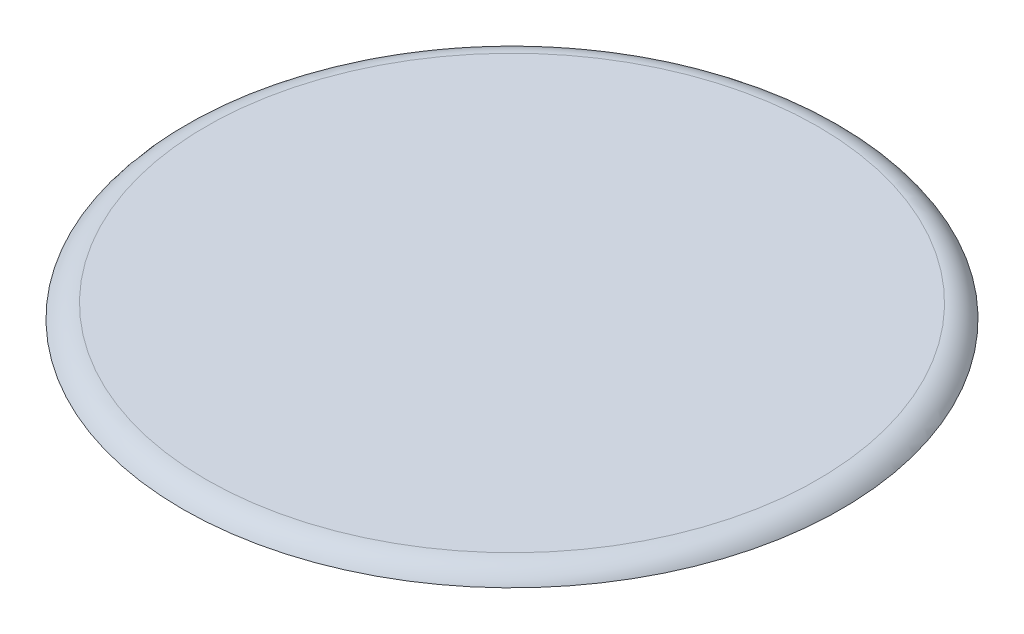
SolidWorks part; units mm, degrees
ref_plane "Front" through (0, 0, 0) normal (0, 0, 1) x (1, 0, 0)
ref_plane "Top" through (0, 0, 0) normal (0, 1, 0) x (1, 0, 0)
ref_plane "Right" through (0, 0, 0) normal (1, 0, 0) x (0, 0, -1)
sketch "Sketch2" plane through (0, 0, 0) normal (0, 1, 0) x (1, 0, 0)
  circle A0 centre (0, 0) radius 61.214
  dimension "D2" = 122.428
extrude "Boss-Extrude1" add sketch "Sketch2" along normal blind 2.54
fillet "Fillet1" radius 5.08 1 edges at (0, 2.54, 61.214)
